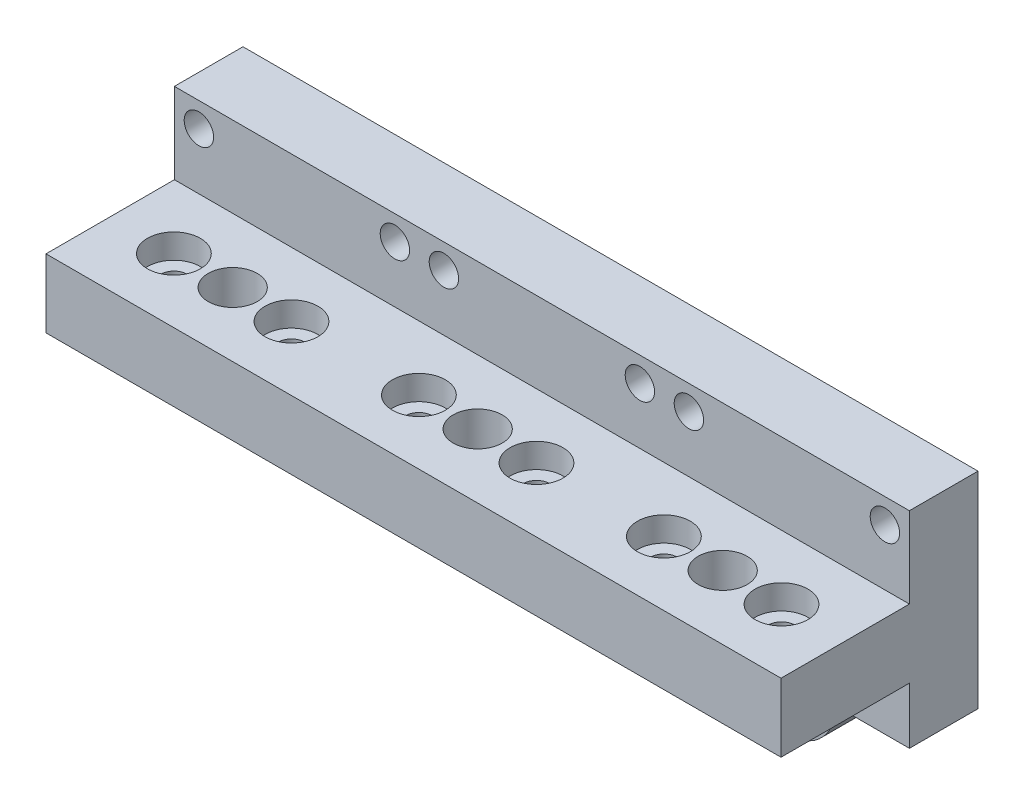
SolidWorks part; units mm, degrees
ref_plane "Front Plane" through (0, 0, 0) normal (0, 0, 1) x (1, 0, 0)
ref_plane "Top Plane" through (0, 0, 0) normal (0, 1, 0) x (1, 0, 0)
ref_plane "Right Plane" through (0, 0, 0) normal (1, 0, 0) x (0, 0, -1)
sketch "Sketch1" plane through (0, 0, 0) normal (0, 0, 1) x (1, 0, 0)
  line L0 (-37.5, 0) -> (-25, 0) construction
  line L1 (37.5, -10.5) -> (30, -10.5)
  line L2 (37.5, -10.5) -> (37.5, 10.5)
  line L3 (37.5, 10.5) -> (-37.5, 10.5)
  line L4 (-37.5, -10.5) -> (-37.5, 10.5)
  line L5 (37.5, -10.5) -> (-37.5, 10.5) construction
  line L6 (37.5, 10.5) -> (-37.5, -10.5) construction
  line L7 (-30, -10.5) -> (-37.5, -10.5)
  line L8 (-25, 0) -> (-12.5, 0) construction
  line L9 (-12.5, 0) -> (0, 0) construction
  line L10 (0, 0) -> (12.5, 0) construction
  line L11 (12.5, 0) -> (25, 0) construction
  line L12 (25, 0) -> (37.5, 0) construction
  line L13 (-5, -10.5) -> (-20, -10.5)
  line L14 (20, -10.5) -> (5, -10.5)
  line L15 (-35, 10.5) -> (-35, 8) construction
  line L16 (-35, 8) -> (-37.5, 8) construction
  line L17 (-25, -10.5) -> (-25, 10.5) construction
  line L18 (-12.5, -10.5) -> (-12.5, 10.5) construction
  line L19 (12.5, -10.5) -> (12.5, 10.5) construction
  arc A0 (-20, -10.5) -> (-30, -10.5) centre (-25, -10.5) cw
  arc A1 (5, -10.5) -> (-5, -10.5) centre (0, -10.5) cw
  arc A2 (30, -10.5) -> (20, -10.5) centre (25, -10.5) cw
  circle A3 centre (-25, -10.5) radius 1.7999
  circle A4 centre (0, -10.5) radius 1.7999
  circle A5 centre (25, -10.5) radius 1.7999
  circle A6 centre (-35, 8) radius 1.5
  circle A7 centre (-15, 8) radius 1.5
  circle A8 centre (-10, 8) radius 1.5
  circle A9 centre (10, 8) radius 1.5
  circle A10 centre (35, 8) radius 1.5
  circle A11 centre (15, 8) radius 1.5
  point P0 (0, 0)
  dimension "D4" = 5
  dimension "D5" = 3.5999
  dimension "D7" = 3
  dimension "D1" = 75
  dimension "D2" = 21
  dimension "D3" = 12.5
  dimension "D6" = 2.5
extrude "Boss-Extrude1" add sketch "Sketch1" along normal blind 7
ref_plane "Plane1" through (0, 2.25, 0) normal (0, 1, 0) x (1, 0, 0)
sketch "Sketch2" plane through (0, 2.25, 0) normal (0, 1, 0) x (1, 0, 0)
  line L1 (-37.5, -13.55) -> (-12.5, -13.55) construction
  line L7 (37.5, -7) -> (-37.5, -7)
  line L8 (37.5, -7) -> (37.5, -20.1)
  line L11 (37.5, -20.1) -> (-37.5, -20.1)
  line L12 (-37.5, -7) -> (-37.5, -20.1)
  line L13 (37.5, -7) -> (-37.5, -20.1) construction
  line L14 (37.5, -20.1) -> (-37.5, -7) construction
  line L15 (-12.5, -13.55) -> (12.5, -13.55) construction
  line L16 (12.5, -13.55) -> (37.5, -13.55) construction
  line L17 (12.5, -13.55) -> (12.5, -7) construction
  line L18 (-12.5, -13.55) -> (-12.5, -7) construction
  circle A0 centre (0, -13.55) radius 2.5
  circle A1 centre (6.0001, -13.55) radius 2.6999
  circle A2 centre (-6.0001, -13.55) radius 2.6999
  circle A3 centre (6.0001, -13.55) radius 1.3498
  circle A4 centre (-6.0001, -13.55) radius 1.3498
  circle A5 centre (-18.9999, -13.55) radius 1.3498
  circle A6 centre (-18.9999, -13.55) radius 2.6999
  circle A7 centre (-25, -13.55) radius 2.5
  circle A8 centre (-31.0001, -13.55) radius 1.3498
  circle A9 centre (-31.0001, -13.55) radius 2.6999
  circle A10 centre (31.0001, -13.55) radius 1.3498
  circle A11 centre (31.0001, -13.55) radius 2.6999
  circle A12 centre (25, -13.55) radius 2.5
  circle A13 centre (18.9999, -13.55) radius 1.3498
  circle A14 centre (18.9999, -13.55) radius 2.6999
  point P4 (0, -13.55)
  dimension "D2" = 5
  dimension "D3" = 5.3999
  dimension "D6" = 2.6997
  dimension "D1" = 13.1
  dimension "D4" = 6.0001
  dimension "D5" = 6.0001
  dimension "D7" = 25
extrude "Boss-Extrude2" add sketch "Sketch2" against normal blind 6.988 contours L7 L12 L11 L8 A11 A9 A7 A2 A1 A0 A6 A12 A14 | A9 A8 | A6 A5 | A2 A4 | A1 A3 | A14 A13 | A11 A10 region at (36.7386, 2.25, 13.55) region at (3.3766, 2.25, 13.55) region at (-8.6237, 2.25, 13.55) region at (-21.6234, 2.25, 13.55) region at (-33.6237, 2.25, 13.55) region at (28.3766, 2.25, 13.55) region at (16.3763, 2.25, 13.55)
extrude "Cut-Extrude1" cut sketch "Sketch2<3>" against normal blind 2.5 contours A9 A8 | A6 A5 | A2 A4 | A1 A3 | A14 A13 | A11 A10 region at (3.3766, 2.25, 13.55) region at (-8.6237, 2.25, 13.55) region at (-21.6234, 2.25, 13.55) region at (-33.6237, 2.25, 13.55) region at (28.3766, 2.25, 13.55) region at (16.3763, 2.25, 13.55)
sketch "Sketch2<3>" plane through (0, 2.25, 0) normal (0, 1, 0) x (1, 0, 0) same geometry as "Sketch2"
ref_plane "Plane2" through (-37.5, -4.738, 7) normal (-1, 0, 0) x (0, 0, 1)
